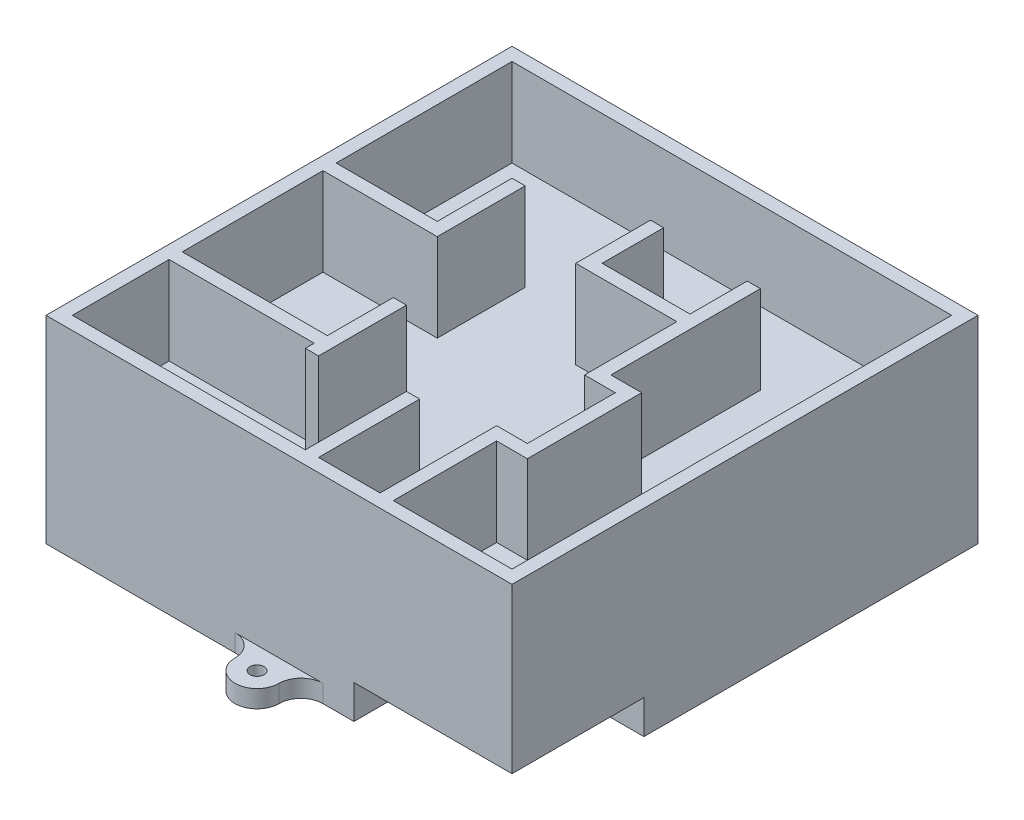
SolidWorks part; units mm, degrees
ref_plane "Front Plane" through (0, 0, 0) normal (0, 0, 1) x (1, 0, 0)
ref_plane "Top Plane" through (0, 0, 0) normal (0, 1, 0) x (1, 0, 0)
ref_plane "Right Plane" through (0, 0, 0) normal (1, 0, 0) x (0, 0, -1)
sketch "Sketch2" plane through (0, 0, 0) normal (0, 1, 0) x (1, 0, 0)
  line L1 (0, 0) -> (106, 0)
  line L2 (0, 0) -> (0, 106)
  line L3 (0, 106) -> (106, 106)
  line L4 (106, 0) -> (106, 106)
  circle A0 centre (18, 15) radius 4
  circle A1 centre (92, 13.5) radius 6
  dimension "D3" = 8
  dimension "D4" = 12
  dimension "D5" = 15
  dimension "D6" = 18
  dimension "D7" = 13.5
  dimension "D8" = 14
  dimension "D1" = 106
  dimension "D2" = 106
extrude "Boss-Extrude1" add sketch "Sketch2" along normal blind 25
sketch "Sketch3" plane through (0, 25, 0) normal (0, 1, 0) x (1, 0, 0)
  line L0 (3, 103) -> (3, 3)
  line L1 (0, 106) -> (106, 106)
  line L2 (0, 106) -> (0, 0)
  line L3 (0, 0) -> (106, 0)
  line L4 (106, 106) -> (106, 0)
  line L5 (3, 3) -> (103, 3)
  line L6 (103, 103) -> (103, 3)
  line L7 (3, 103) -> (103, 103)
  dimension "D1" = 3
extrude "Boss-Extrude2" add sketch "Sketch3" along normal blind 20
sketch "Sketch5" plane through (0, 25, 0) normal (0, 1, 0) x (1, 0, 0)
  line L2 (3, 28) -> (3, 25)
  line L5 (3, 103) -> (3, 3) construction
  line L6 (83, 52.5) -> (83, 26.5)
  line L9 (36, 43) -> (39, 43)
  line L10 (39, 23) -> (39, 43)
  line L12 (3, 63) -> (3, 60)
  line L19 (26, 63) -> (26, 80)
  line L20 (3, 3) -> (103, 3) construction
  line L21 (56, 3) -> (59, 3)
  line L22 (56, 3) -> (56, 26)
  line L23 (56, 26) -> (59, 26)
  line L24 (59, 3) -> (59, 26)
  line L25 (3, 28) -> (36, 28)
  line L26 (3, 3) -> (103, 3) construction
  line L27 (73, 3) -> (76, 3)
  line L30 (76, 3) -> (76, 26.5)
  line L38 (80, 29.5) -> (80, 49.5)
  line L41 (80, 49.5) -> (73, 49.5)
  line L42 (73, 52.5) -> (73, 49.5)
  line L44 (76, 26.5) -> (83, 26.5)
  line L45 (73, 52.5) -> (83, 52.5)
  line L47 (3, 63) -> (26, 63)
  line L50 (80, 29.5) -> (73, 29.5)
  line L51 (73, 29.5) -> (73, 3)
  line L52 (29, 60) -> (3, 60)
  line L53 (29, 60) -> (29, 80)
  line L54 (29, 80) -> (26, 80)
  line L55 (36, 43) -> (36, 28)
  line L56 (3, 25) -> (36, 25)
  line L57 (36, 25) -> (36, 23)
  line L58 (36, 23) -> (39, 23)
  dimension "D3" = 0
extrude "Boss-Extrude3" add sketch "Sketch5" along normal blind 20 contours L9 L10 L58 L57 L56 L2 L25 L55 | L54 L19 L47 L12 L52 L53 | L22 L21 L24 L23 | L51 L27 L30 L44 L6 L45 L42 L41 L38 L50
sketch "Sketch7" plane through (0, 25, 0) normal (0, 1, 0) x (1, 0, 0)
  line L1 (73, 52.5) -> (76, 52.5)
  line L2 (73, 52.5) -> (73, 86.5)
  line L3 (73, 86.5) -> (76, 86.5)
  line L4 (76, 52.5) -> (76, 86.5)
  line L5 (73, 73.4965) -> (53, 73.4965)
  line L6 (73, 73.4965) -> (73, 70.4965)
  line L7 (73, 70.4965) -> (53, 70.4965)
  line L8 (53, 73.4965) -> (53, 70.4965)
  line L9 (53, 70.4965) -> (50, 70.4965)
  line L10 (53, 70.4965) -> (53, 87.4965)
  line L11 (53, 87.4965) -> (50, 87.4965)
  line L12 (50, 70.4965) -> (50, 87.4965)
  line M14 (73, 52.5) -> (83, 52.5)
  dimension "D1" = 3
  dimension "D2" = 3
  dimension "D3" = 3
  dimension "D4" = 34
  dimension "D5" = 20
  dimension "D6" = 17
extrude "Boss-Extrude4" add sketch "Sketch7" along normal blind 20 contours L12 L9 L8 L10 L11 | L5 L8 L7 L2 | L4 L3 L2 M14 region at (74.5, 25, -69.5) region at (63, 25, -71.9965) region at (51.5, 25, -78.9965)
sketch "Sketch9" plane through (0, 25, 0) normal (0, 1, 0) x (1, 0, 0)
  circle A0 centre (92, 13.5) radius 9.9058
extrude "Cut-Extrude1" [suppressed] cut sketch "Sketch9" against normal blind 10
fillet "Fillet1" [suppressed] radius 5
sketch "Sketch10" plane through (0, 0, 0) normal (0, 0, 1) x (1, 0, 0)
  line L0 (0, 0) -> (106, 0) construction
  line L1 (48, 4) -> (58, 4)
  line L2 (48, 4) -> (48, 0)
  line L3 (48, 0) -> (58, 0)
  line L4 (58, 4) -> (58, 0)
  line L5 (0, 45) -> (106, 45) construction
  point P6 (53, 4)
  point P9 (53, 45)
  dimension "D1" = 10
  dimension "D2" = 4
  dimension "D3" = 0
  dimension "D4" = 0
extrude "Boss-Extrude5" add sketch "Sketch10" along normal blind 10
sketch "Sketch11" plane through (0, 0, -106) normal (0, 0, -1) x (-1, 0, 0)
  line L0 (-106, 45) -> (0, 45) construction
  line L1 (-58, 4) -> (-48, 4)
  line L2 (-58, 4) -> (-58, 0)
  line L3 (-58, 0) -> (-48, 0)
  line L4 (-48, 4) -> (-48, 0)
  line L5 (-106, 0) -> (0, 0) construction
  point P4 (-53, 4)
  point P7 (-53, 45)
  dimension "D1" = 10
  dimension "D2" = 4
  dimension "D3" = 0
  dimension "D4" = 0
extrude "Boss-Extrude6" add sketch "Sketch11" along normal blind 10
fillet "Fillet2" 2 edges at (48, 2, -116) (58, 2, -116) type full round first side face at (48, 2, -111) second side face at (58, 2, -111) middle face at (53, 2, -116)
fillet "Fillet3" radius 5 2 edges at (48, 2, -106) (58, 2, -106)
fillet "Fillet4" radius 5 2 edges at (48, 2, 0) (58, 2, 0)
fillet "Fillet5" 2 edges at (48, 2, 10) (58, 2, 10) type full round first side face at (48, 2, 7.5) second side face at (58, 2, 7.5) middle face at (53, 2, 10)
sketch "Sketch13" plane through (0, 4, 0) normal (0, 1, 0) x (1, 0, 0)
  circle A0 centre (53, -5) radius 1.6
  circle A1 centre (53, 111) radius 1.6
  dimension "D1" = 3.2
  dimension "D2" = 3.2
extrude "Cut-Extrude2" cut sketch "Sketch13" against normal through all
sketch "Sketch14" plane through (0, 0, 0) normal (0, 0, 1) x (1, 0, 0)
  line L1 (106, 0) -> (70.0395, 0)
  line L2 (106, 0) -> (106, 7.6935)
  line L3 (106, 7.6935) -> (70.0395, 7.6935)
  line L4 (70.0395, 0) -> (70.0395, 7.6935)
extrude "Cut-Extrude3" cut sketch "Sketch14" against normal blind 30
